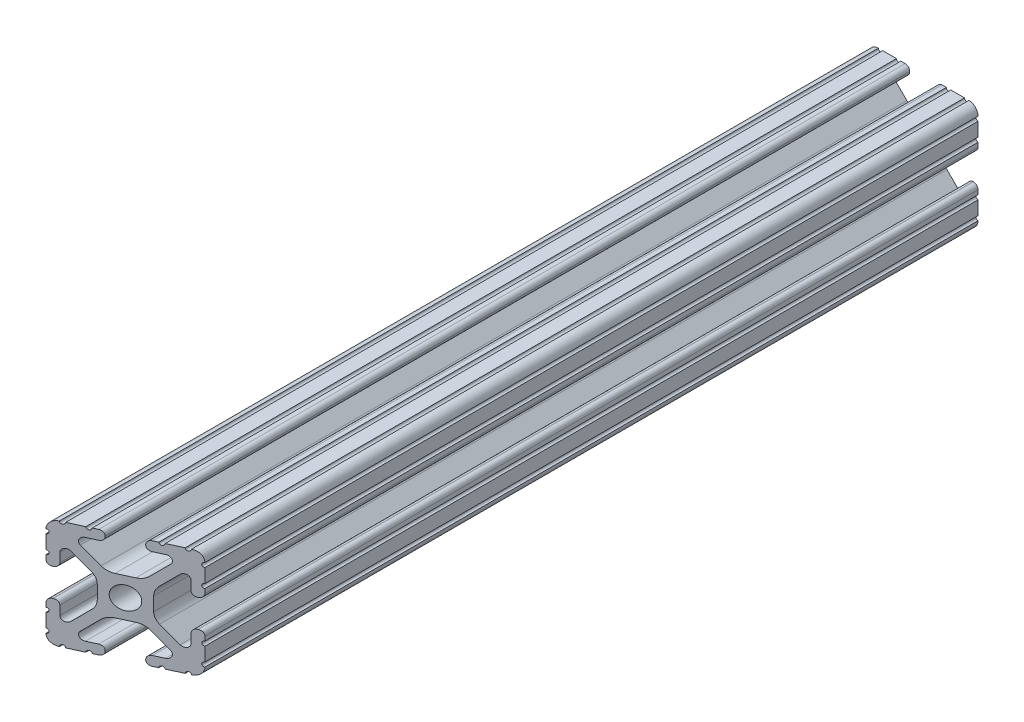
SolidWorks part; units mm, degrees
ref_plane "Front Plane" through (0, 0, 0) normal (0, 0, 1) x (1, 0, 0)
ref_plane "Top Plane" through (0, 0, 0) normal (0, 1, 0) x (1, 0, 0)
ref_plane "Right Plane" through (0, 0, 0) normal (1, 0, 0) x (0, 0, -1)
sketch "Sketch1" plane through (0, 0, 0) normal (0, 0, 1) x (1, 0, 0)
  line L88 (-7.1797, -8.6452) -> (-3.9523, -5.4237)
  line L89 (-1.7093, -4.4958) -> (1.7093, -4.4958)
  line L90 (3.9523, -5.4237) -> (7.1797, -8.6452)
  line L91 (6.4164, -10.4902) -> (4.2875, -10.4902)
  line L92 (3.2385, -11.5392) -> (3.2385, -11.651)
  line L93 (4.2875, -12.7) -> (5.3171, -12.7)
  line L94 (6.3331, -12.7) -> (9.5504, -12.7)
  line L95 (12.7, -9.5504) -> (12.7, -6.3331)
  line L96 (12.7, -5.3171) -> (12.7, -4.2875)
  line L97 (11.651, -3.2385) -> (11.5392, -3.2385)
  line L98 (10.4902, -4.2875) -> (10.4902, -6.4021)
  line L99 (8.7371, -7.1294) -> (5.441, -3.8408)
  line L100 (4.5085, -1.5932) -> (4.5085, 1.5932)
  line L101 (5.441, 3.8408) -> (8.7371, 7.1294)
  line L102 (10.4902, 6.4021) -> (10.4902, 4.2875)
  line L103 (11.5392, 3.2385) -> (11.651, 3.2385)
  line L104 (12.7, 4.2875) -> (12.7, 5.3171)
  line L105 (12.7, 6.3331) -> (12.7, 9.5504)
  line L106 (9.5504, 12.7) -> (6.3331, 12.7)
  line L107 (5.3171, 12.7) -> (4.2875, 12.7)
  line L108 (3.2385, 11.651) -> (3.2385, 11.5392)
  line L109 (4.2875, 10.4902) -> (6.4768, 10.4902)
  line L110 (7.207, 8.7244) -> (3.8983, 5.4232)
  line L111 (1.6558, 4.4958) -> (-1.6558, 4.4958)
  line L112 (-3.8983, 5.4232) -> (-7.207, 8.7244)
  line L113 (-6.4768, 10.4902) -> (-4.2875, 10.4902)
  line L114 (-3.2385, 11.5392) -> (-3.2385, 11.651)
  line L115 (-4.2875, 12.7) -> (-5.3171, 12.7)
  line L116 (-6.3331, 12.7) -> (-9.5504, 12.7)
  line L117 (-12.7, 9.5504) -> (-12.7, 6.3331)
  line L118 (-12.7, 5.3171) -> (-12.7, 4.2875)
  line L119 (-11.651, 3.2385) -> (-11.5392, 3.2385)
  line L120 (-10.4902, 4.2875) -> (-10.4902, 6.4021)
  line L121 (-8.7371, 7.1294) -> (-5.441, 3.8408)
  line L122 (-4.5085, 1.5932) -> (-4.5085, -1.5932)
  line L123 (-5.441, -3.8408) -> (-8.7371, -7.1294)
  line L124 (-10.4902, -6.4021) -> (-10.4902, -4.2875)
  line L125 (-11.5392, -3.2385) -> (-11.651, -3.2385)
  line L126 (-12.7, -4.2875) -> (-12.7, -5.3171)
  line L127 (-12.7, -6.3331) -> (-12.7, -9.5504)
  line L128 (-9.5504, -12.7) -> (-6.3331, -12.7)
  line L129 (-5.3171, -12.7) -> (-4.2875, -12.7)
  line L130 (-3.2385, -11.651) -> (-3.2385, -11.5392)
  line L131 (-4.2875, -10.4902) -> (-6.4164, -10.4902)
  circle A1 centre (0, 0) radius 2.6035
  arc A104 (-7.1797, -8.6452) -> (-6.4164, -10.4902) centre (-6.4164, -9.4098) ccw
  arc A105 (-1.7093, -4.4958) -> (-3.9523, -5.4237) centre (-1.7093, -7.6708) ccw
  arc A106 (3.9523, -5.4237) -> (1.7093, -4.4958) centre (1.7093, -7.6708) ccw
  arc A107 (6.4164, -10.4902) -> (7.1797, -8.6452) centre (6.4164, -9.4098) ccw
  arc A108 (4.2875, -10.4902) -> (3.2385, -11.5392) centre (4.2875, -11.5392) ccw
  arc A109 (3.2385, -11.651) -> (4.2875, -12.7) centre (4.2875, -11.651) ccw
  arc A110 (6.3331, -12.7) -> (5.3171, -12.7) centre (5.8251, -12.7) ccw
  arc A111 (10.5664, -12.6998) -> (9.5504, -12.7) centre (10.0584, -12.7) ccw
  arc A112 (10.5664, -12.6998) -> (12.6998, -10.5664) centre (10.5918, -10.5918) ccw
  arc A113 (12.7, -9.5504) -> (12.6998, -10.5664) centre (12.7, -10.0584) ccw
  arc A114 (12.7, -5.3171) -> (12.7, -6.3331) centre (12.7, -5.8251) ccw
  arc A115 (12.7, -4.2875) -> (11.651, -3.2385) centre (11.651, -4.2875) ccw
  arc A116 (11.5392, -3.2385) -> (10.4902, -4.2875) centre (11.5392, -4.2875) ccw
  arc A117 (8.7371, -7.1294) -> (10.4902, -6.4021) centre (9.4628, -6.4021) ccw
  arc A118 (4.5085, -1.5932) -> (5.441, -3.8408) centre (7.6835, -1.5932) ccw
  arc A119 (5.441, 3.8408) -> (4.5085, 1.5932) centre (7.6835, 1.5932) ccw
  arc A120 (10.4902, 6.4021) -> (8.7371, 7.1294) centre (9.4628, 6.4021) ccw
  arc A121 (10.4902, 4.2875) -> (11.5392, 3.2385) centre (11.5392, 4.2875) ccw
  arc A122 (11.651, 3.2385) -> (12.7, 4.2875) centre (11.651, 4.2875) ccw
  arc A123 (12.7, 6.3331) -> (12.7, 5.3171) centre (12.7, 5.8251) ccw
  arc A124 (12.6998, 10.5664) -> (12.7, 9.5504) centre (12.7, 10.0584) ccw
  arc A125 (12.6998, 10.5664) -> (10.5664, 12.6998) centre (10.5918, 10.5918) ccw
  arc A126 (9.5504, 12.7) -> (10.5664, 12.6998) centre (10.0584, 12.7) ccw
  arc A127 (5.3171, 12.7) -> (6.3331, 12.7) centre (5.8251, 12.7) ccw
  arc A128 (4.2875, 12.7) -> (3.2385, 11.651) centre (4.2875, 11.651) ccw
  arc A129 (3.2385, 11.5392) -> (4.2875, 10.4902) centre (4.2875, 11.5392) ccw
  arc A130 (7.207, 8.7244) -> (6.4768, 10.4902) centre (6.4768, 9.4563) ccw
  arc A131 (1.6558, 4.4958) -> (3.8983, 5.4232) centre (1.6558, 7.6708) ccw
  arc A132 (-3.8983, 5.4232) -> (-1.6558, 4.4958) centre (-1.6558, 7.6708) ccw
  arc A133 (-6.4768, 10.4902) -> (-7.207, 8.7244) centre (-6.4768, 9.4563) ccw
  arc A134 (-4.2875, 10.4902) -> (-3.2385, 11.5392) centre (-4.2875, 11.5392) ccw
  arc A135 (-3.2385, 11.651) -> (-4.2875, 12.7) centre (-4.2875, 11.651) ccw
  arc A136 (-6.3331, 12.7) -> (-5.3171, 12.7) centre (-5.8251, 12.7) ccw
  arc A137 (-10.5664, 12.6998) -> (-9.5504, 12.7) centre (-10.0584, 12.7) ccw
  arc A138 (-10.5664, 12.6998) -> (-12.6998, 10.5664) centre (-10.5918, 10.5918) ccw
  arc A139 (-12.7, 9.5504) -> (-12.6998, 10.5664) centre (-12.7, 10.0584) ccw
  arc A140 (-12.7, 5.3171) -> (-12.7, 6.3331) centre (-12.7, 5.8251) ccw
  arc A141 (-12.7, 4.2875) -> (-11.651, 3.2385) centre (-11.651, 4.2875) ccw
  arc A142 (-11.5392, 3.2385) -> (-10.4902, 4.2875) centre (-11.5392, 4.2875) ccw
  arc A143 (-8.7371, 7.1294) -> (-10.4902, 6.4021) centre (-9.4628, 6.4021) ccw
  arc A144 (-4.5085, 1.5932) -> (-5.441, 3.8408) centre (-7.6835, 1.5932) ccw
  arc A145 (-5.441, -3.8408) -> (-4.5085, -1.5932) centre (-7.6835, -1.5932) ccw
  arc A146 (-10.4902, -6.4021) -> (-8.7371, -7.1294) centre (-9.4628, -6.4021) ccw
  arc A147 (-10.4902, -4.2875) -> (-11.5392, -3.2385) centre (-11.5392, -4.2875) ccw
  arc A148 (-11.651, -3.2385) -> (-12.7, -4.2875) centre (-11.651, -4.2875) ccw
  arc A149 (-12.7, -6.3331) -> (-12.7, -5.3171) centre (-12.7, -5.8251) ccw
  arc A150 (-12.6998, -10.5664) -> (-12.7, -9.5504) centre (-12.7, -10.0584) ccw
  arc A151 (-12.6998, -10.5664) -> (-10.5664, -12.6998) centre (-10.5918, -10.5918) ccw
  arc A152 (-9.5504, -12.7) -> (-10.5664, -12.6998) centre (-10.0584, -12.7) ccw
  arc A153 (-5.3171, -12.7) -> (-6.3331, -12.7) centre (-5.8251, -12.7) ccw
  arc A154 (-4.2875, -12.7) -> (-3.2385, -11.651) centre (-4.2875, -11.651) ccw
  arc A155 (-3.2385, -11.5392) -> (-4.2875, -10.4902) centre (-4.2875, -11.5392) ccw
extrude "Boss-Extrude1" add sketch "Sketch1" along normal mid plane 289.56
sketch "Sketch2" plane through (0, 12.7, 0) normal (0, 1, 0) x (1, 0, 0)
  line L0 (-12.7, -144.78) -> (-12.7, 144.78) construction
  line L1 (-6.3331, -144.78) -> (-9.5504, -144.78) construction
  line L2 (9.5504, -144.78) -> (6.3331, -144.78) construction
  line L3 (12.7, -144.78) -> (12.7, 144.78) construction
  line L4 (-12.7, -144.78) -> (-12.7, 144.78) construction
  line L5 (-6.3331, -144.78) -> (-9.5504, -144.78) construction
  line L6 (9.5504, -144.78) -> (6.3331, -144.78) construction
  line L7 (12.7, -144.78) -> (12.7, 144.78) construction
  line L8 (12.7, -144.78) -> (-12.7, -144.78)
  line L9 (-12.7, -144.78) -> (-12.7, -47.4328)
  line L10 (-12.7, -47.4328) -> (12.7, -35.7267)
  line L11 (12.7, -35.7267) -> (12.7, -144.78)
  line L12 (-139.7, -111.5568) -> (6.35, -44.2468) construction
  line L13 (-139.7, -111.5568) -> (6.35, -44.2468) construction
  dimension "D1" = 5.08
extrude "Cut-Extrude1" cut sketch "Sketch2" against normal through all
